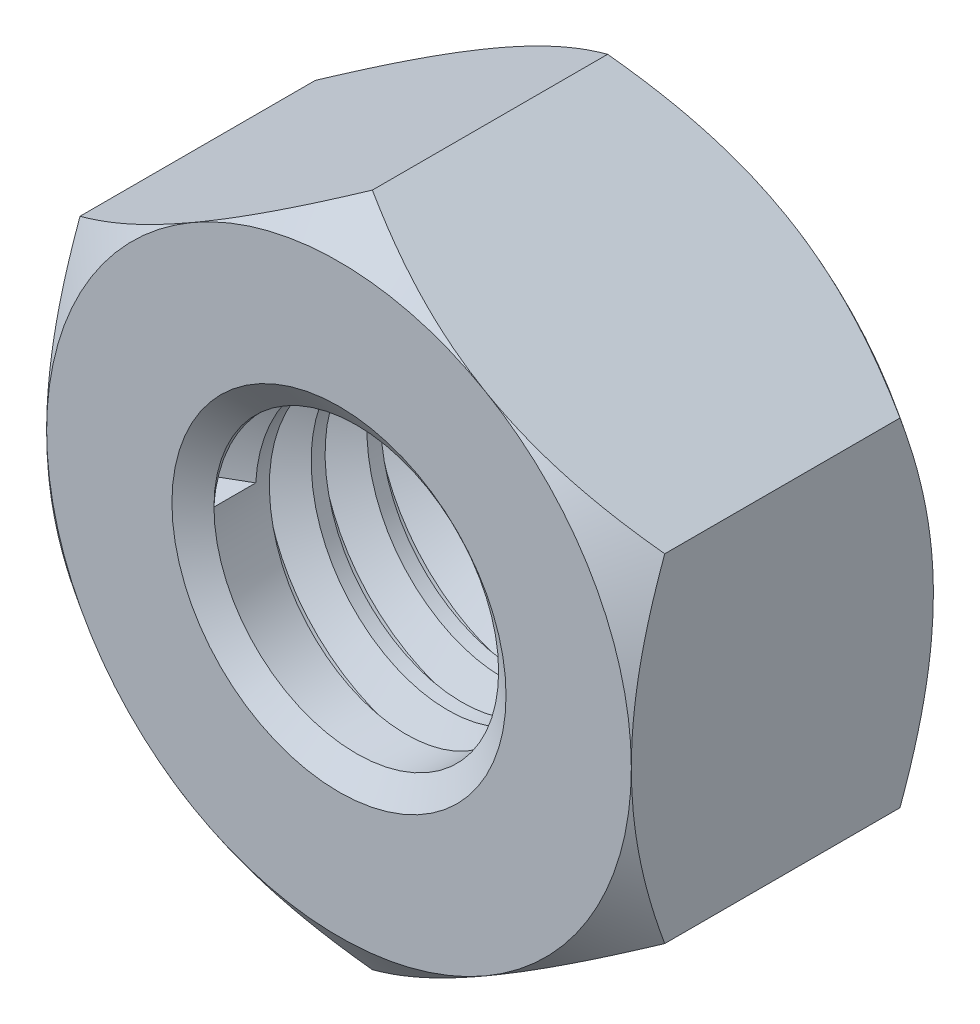
SolidWorks part; units mm, degrees
extrude "BaseNut" add sketch "BaseNutSke" against normal blind 5.7404
sketch "BaseNutSke" plane through (0, 0, 0) normal (0, 0, 1) x (1, 0, 0)
  line L6 (5.5562, 3.2079) -> (5.5562, -3.2079)
  line L7 (-5.5562, 3.2079) -> (-5.5562, -3.2079)
  line L8 (5.5562, 3.2079) -> (0, 6.4158)
  line L9 (0, 6.4158) -> (-5.5562, 3.2079)
  line L10 (-5.5562, -3.2079) -> (0, -6.4158)
  line L11 (0, -6.4158) -> (5.5562, -3.2079)
  circle A0 centre (0, 0) radius 2.7051
  dimension "D2" = 5.5562
  dimension "D3" = 5.5562
  dimension "D1" = 120
  dimension "D4" = 5.5562
cosmetic thread "ThreadCosmetic" [suppressed] parameters "Thread_major"=6.35
pattern_linear "ThdSchPat" [suppressed]
revolve "ThreadSchematic" [suppressed] cut sketch "ThdSchSke" angle 360 about L6
sketch "ThdSchSke" plane through (0, 0, 0) normal (0, 1, 0) x (1, 0, 0)
  line L0 (-3.175, 0.0254) -> (-2.7051, 0.3544)
  line L1 (-2.7051, 0.3544) -> (-1.3525, 0.3544)
  line L2 (-1.3525, 0.3544) -> (-1.3525, -0.3036)
  line L3 (-1.3525, -0.3036) -> (-2.7051, -0.3036)
  line L4 (-2.7051, -0.3036) -> (-3.175, 0.0254)
  line L5 (-3.175, 0.9068) -> (3.175, 0.9068) construction
  line L6 (0, 0.9068) -> (0, -2.9874) construction
  line L7 (0, 5.386) -> (0, 0.329) construction
  dimension "SideAngle" = 55
  dimension "Advance" = 0.9068
  dimension "D1" = 0.0254
ref_plane "Plane1" through (0, 0, 0) normal (0, 0, 1) x (1, 0, 0)
ref_plane "Plane2" through (0, 0, 0) normal (0, 1, 0) x (1, 0, 0)
ref_plane "Plane3" through (0, 0, 0) normal (1, 0, 0) x (0, 0, -1)
sketch "Sketch4" plane through (0, 0, 0) normal (1, 0, 0) x (0, 0, -1)
  line L0 (5.7404, 5.5563) -> (5.334, 5.5563)
  line L1 (5.7404, 5.5563) -> (5.7404, 19.1158)
  line L2 (5.334, 19.1158) -> (5.7404, 19.1158)
  line L3 (5.334, 19.1158) -> (5.334, 5.5563)
  line L4 (0, 0) -> (34.925, 0) construction
  line L6 (5.7404, 3.2079) -> (5.7404, 6.4158) construction
  line L7 (0, 5.5563) -> (-12.7, 5.5562)
  line L8 (0, 3.2079) -> (0, 6.4158) construction
  line L9 (0.635, 6.4158) -> (0.635, 19.1158)
  line L10 (0.635, 19.1158) -> (-12.7, 19.1158)
  line L11 (-12.7, 19.1158) -> (-12.7, 5.5562)
  line L12 (0, 5.5563) -> (0.635, 6.4158)
  line L14 (0, 3.2079) -> (0, -3.2079) construction
  line L15 (5.7404, 6.4158) -> (0, 6.4158) construction
  dimension "D1" = 5.5562
  dimension "D2" = 0.635
  dimension "D3" = 12.7
  dimension "D4" = 12.7
revolve "Bearing-Face" [suppressed] cut sketch "Sketch4" angle 360 about L4
sketch "Sketch3" plane through (0, 0, 0) normal (1, 0, 0) x (0, 0, -1)
  line L0 (5.7404, 5.5563) -> (5.1054, 6.4158)
  line L1 (5.1054, 6.4158) -> (5.1054, 19.1158)
  line L2 (5.1054, 19.1158) -> (18.4404, 19.1158)
  line L3 (18.4404, 19.1158) -> (18.4404, 5.5563)
  line L4 (18.4404, 5.5563) -> (5.7404, 5.5563)
  line L5 (5.7404, 3.2079) -> (5.7404, 6.4158) construction
  line L6 (5.7404, 6.4158) -> (0, 6.4158) construction
  line L7 (0, 0) -> (38.6776, 0) construction
  line L8 (5.7404, 0) -> (0, 0) construction
  line L9 (2.8702, 6.4158) -> (2.8702, 44.222) construction
  line L10 (0.635, 19.1158) -> (-12.7, 19.1158)
  line L11 (-12.7, 19.1158) -> (-12.7, 5.5563)
  line L12 (-12.7, 5.5563) -> (0, 5.5563)
  line L13 (0, 5.5563) -> (0.635, 6.4158)
  line L14 (0.635, 6.4158) -> (0.635, 19.1158)
  line L16 (5.7404, 6.4158) -> (0, 6.4158) construction
  dimension "D1" = 5.5562
  dimension "D2" = 0.635
  dimension "D4" = 12.7
  dimension "D3" = 12.7
revolve "Double-Chamfer" cut sketch "Sketch3" angle 360 about L7
sketch "Sketch5" plane through (0, 0, 0) normal (1, 0, 0) x (0, 0, -1)
  line L0 (5.715, 3.175) -> (5.3531, 2.6581)
  line L1 (5.7658, 3.175) -> (5.715, 3.175)
  line L2 (5.7658, 3.175) -> (5.7658, 2.6581)
  line L3 (5.7658, 2.6581) -> (5.3531, 2.6581)
  line L6 (-0.0508, 3.175) -> (0, 3.175)
  line L7 (0, 3.175) -> (0.3619, 2.6581)
  line L9 (0.3619, 2.6581) -> (-0.0508, 2.6581)
  line L10 (-0.0508, 2.6581) -> (-0.0508, 3.175)
  line L11 (25.0375, 0) -> (38.388, 0) construction
  line L12 (5.7404, 0) -> (0, 0) construction
  dimension "D1" = 35
  dimension "D2" = 0.0508
  dimension "ThreadMajor" = 3.175
  dimension "Offset1" = 5.7658
revolve "EndChamfer" cut sketch "Sketch5" angle 360 about L11
thread "Thread1" pitch 1.0583 method cut profile "Thread Profile1" start angle 0, offset 0, length 0, pitch 1.0583, diameter 5.4102
ref_plane "Plane4" through (-2.7051, 0, -0.329) normal (0, -1, 0) x (-1, 0, 0)
sketch "Thread Profile1" plane through (-2.7051, 0, -0.329) normal (0, -1, 0) x (-1, 0, 0)
  line L0 (0, 0) -> (0, 1.0583) construction
  line L1 (0, 0) -> (0.5728, 0.3307)
  line L2 (0.5728, 0.3307) -> (0.5728, 0.463)
  line L3 (0.5728, 0.463) -> (0, 0.7937)
  line L4 (0.5728, 0.3969) -> (0, 0.3969) construction
  line L11 (0, 0) -> (0, 0.7937)
  point P2 (0, 0)
  dimension "Pitch" = 1.0583
  dimension "Profile_Angle" = 60
  dimension "Profile_Land" = 0.1323
  dimension "Profile_Height" = 0.5728
equation "\"D2@BaseNutSke\" = \"Width_flats@BaseNutSke\" / 2"
equation "\"D3@BaseNutSke\" = \"Width_flats@BaseNutSke\" / 2"
equation "\"D1@Sketch3\" = \"Width_flats@BaseNutSke\" /2"
equation "\"D2@Sketch3\" = \"Thread_major@ThreadCosmetic\" *.1"
equation "\"D1@Sketch4\" = \"D2@BaseNutSke\""
equation "\"D2@Sketch4\" = \"Thread_major@ThreadCosmetic\" *.10"
equation "\"D4@BaseNutSke\" = \"D3@BaseNutSke\""
equation "\"Thread_major@ThdSchSke\" = \"Thread_major@ThreadCosmetic\""
equation "\"Tap_Drill@ThdSchSke\" = \"Tap_drill@BaseNutSke\""
equation "\"OverCut@ThdSchSke\" = \"Tap_Drill@ThdSchSke\" * 0.5"
equation "\"Num_threads@ThdSchPat\" = int(  ( \"Thickness@BaseNut\" - 0.002 ) / \"Advance@ThdSchSke\" + 0.999 )  + 1"
equation "\"Advance@ThdSchPat\" = ( \"Thickness@BaseNut\" - 0.002 ) /  (\"Num_threads@ThdSchPat\" - 1) 'relax it"
equation "' \"Num_threads@ThdSchPat\" = \"Num_threads@ThdSchPat\" - sgn( \"Num_threads@ThdSchPat\" - 1) '---chamfered tips only---"
equation "\"ThreadMajor@Sketch5\" = \"Thread_major@ThreadCosmetic\" * 0.5"
equation "\"ChamferDepth@Sketch5\" = (\"Thread_major@ThreadCosmetic\" - \"Tap_drill@BaseNutSke\") * 0.55"
equation "\"Offset1@Sketch5\" = \"Thickness@BaseNut\" + 0.001"
equation "\"Offset2@Sketch5\" = \"Offset1@Sketch5\" + 0.002"
